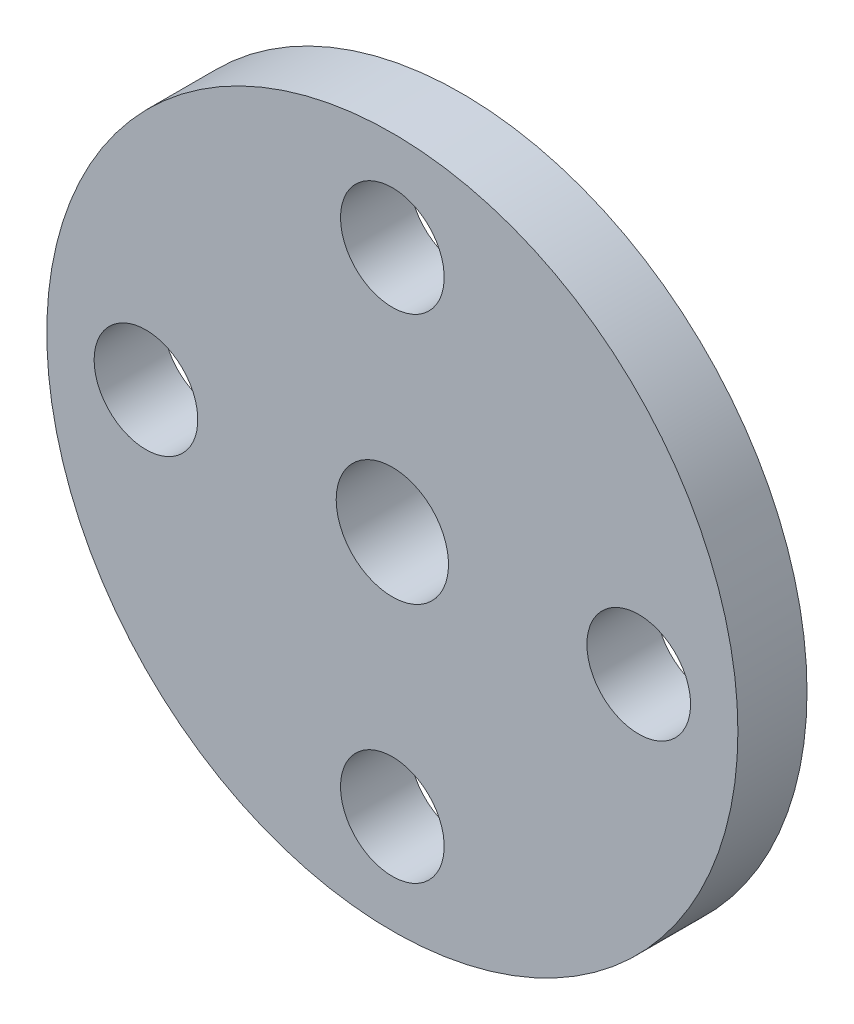
SolidWorks part; units mm, degrees
ref_plane "Piano frontale" through (0, 0, 0) normal (0, 0, 1) x (1, 0, 0)
ref_plane "Piano superiore" through (0, 0, 0) normal (0, 1, 0) x (1, 0, 0)
ref_plane "Piano destro" through (0, 0, 0) normal (1, 0, 0) x (0, 0, -1)
sketch "Schizzo14" plane through (0, 0, 0) normal (0, 0, 1) x (1, 0, 0)
  line L0 (0, 10) -> (0, -10) construction
  line L1 (0, -10) -> (-10, 0) construction
  line L2 (-10, 0) -> (10, 0) construction
  circle A0 centre (0, 0) radius 10
  dimension "D1" = 20
extrude "Estrusione-Estrusione2" add sketch "Schizzo14" along normal blind 2
hole_wizard "Foro Ø3.0 (3)-1" positions "Schizzo3D14" profile "Schizzo18" hole size "Ø3.0" standard "ISO" end condition through all
sketch3d "Schizzo3D14"
  point P0 (7.13, 0, 0)
  point P2 (-7.13, 0, 0)
  point P4 (0, -7.13, 0)
  point P6 (0, 7.13, 0)
  dimension "D1" = 7.13
  dimension "D2" = 7.13
  dimension "D3" = 7.13
  dimension "D4" = 7.13
sketch "Schizzo18" plane through (7.13, 0, 0) normal (1, 0, 0) x (0, 1, 0)
  line L0 (0, 0) -> (0, 2)
  line L1 (0, 2) -> (1.5, 2)
  line L2 (1.5, 2) -> (1.5, 0)
  line L5 (1.5, 0) -> (0, 0)
  line L11 (0, -6.35) -> (0, 107.95) construction
  dimension "Thru Hole Dia." = 3
  dimension "Thru Hole Depth" = 2
cosmetic thread "Filettatura cosmetica2" parameters "D1"=1.9999, "D2"=3
cosmetic thread "Filettatura cosmetica3" parameters "D1"=1.9999, "D2"=3
cosmetic thread "Filettatura cosmetica4" parameters "D1"=1.9999, "D2"=3
cosmetic thread "Filettatura cosmetica5" parameters "D1"=1.9999, "D2"=3
sketch "Schizzo19" plane through (0, 0, 0) normal (0, 0, 1) x (1, 0, 0)
  circle A0 centre (0, 0) radius 4.5
  dimension "D1" = 9
extrude "Estrusione-Estrusione3" add sketch "Schizzo19" against normal blind 2
sketch "Schizzo20" plane through (0, 0, -2) normal (0, 0, -1) x (-1, 0, 0)
  circle A0 centre (0, 0) radius 1.625
  dimension "D1" = 3.25
extrude "Taglio-Estrusione1" cut sketch "Schizzo20" against normal through all
